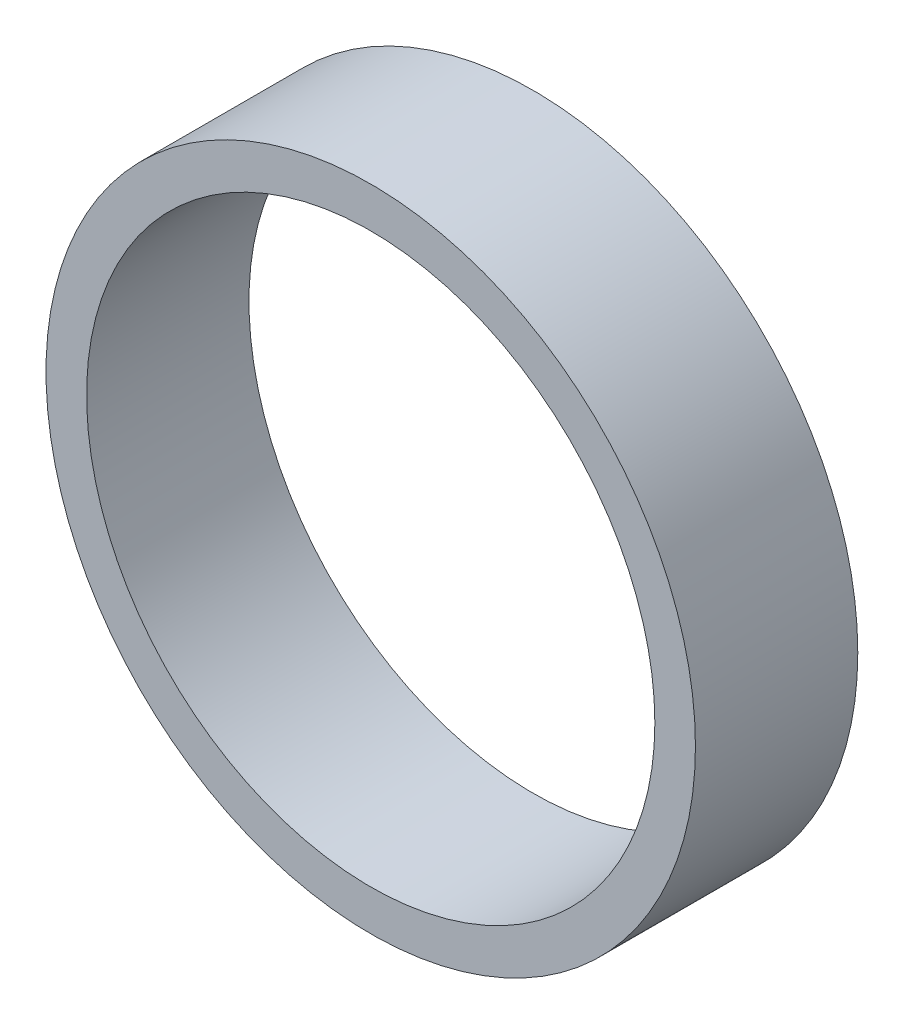
SolidWorks part; units mm, degrees
material "Leaded Commercial Bronze"
ref_plane "Front Plane" through (0, 0, 0) normal (0, 0, 1) x (1, 0, 0)
ref_plane "Top Plane" through (0, 0, 0) normal (0, 1, 0) x (1, 0, 0)
ref_plane "Right Plane" through (0, 0, 0) normal (1, 0, 0) x (0, 0, -1)
sketch "Sketch1" plane through (0, 0, 0) normal (0, 0, 1) x (1, 0, 0)
  circle A0 centre (0, 0) radius 50.8
  circle A1 centre (0, 0) radius 44.45
  dimension "D1" = 101.6
  dimension "D2" = 88.9
extrude "Boss-Extrude1" add sketch "Sketch1" along normal blind 25.4
